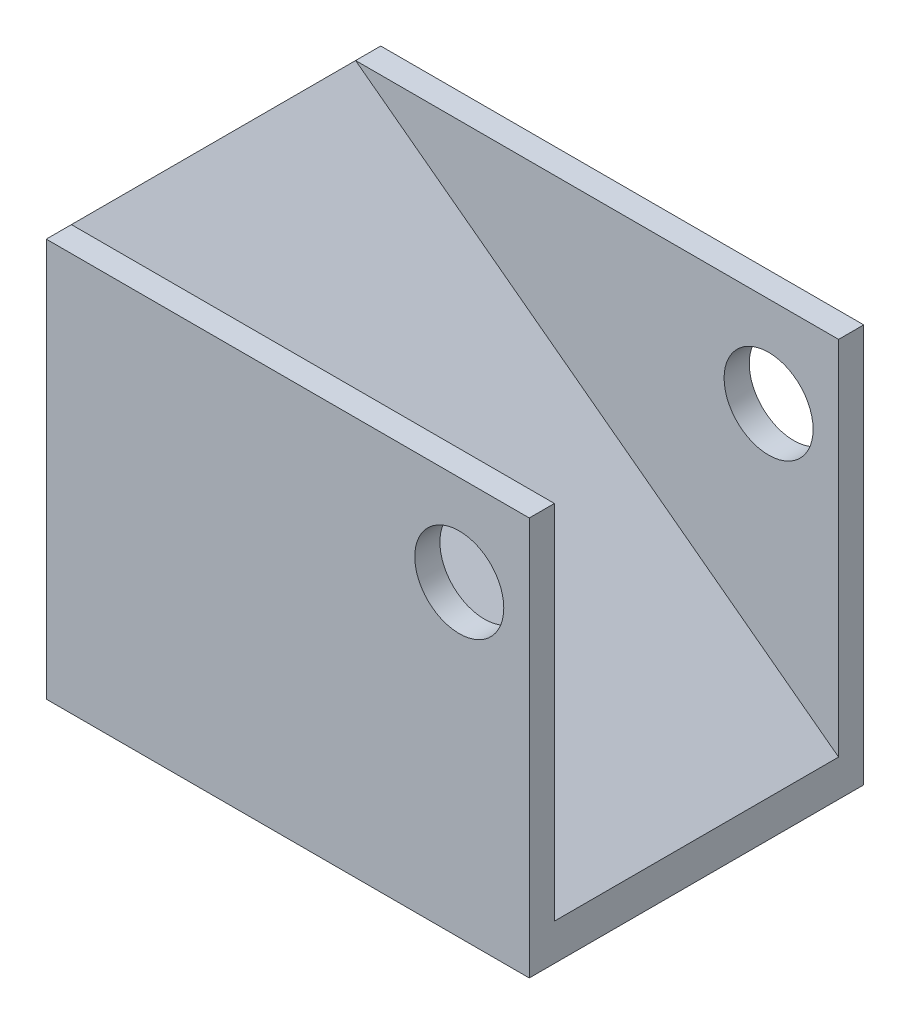
SolidWorks part; units mm, degrees
ref_plane "Front Plane" through (0, 0, 0) normal (0, 0, 1) x (1, 0, 0)
ref_plane "Top Plane" through (0, 0, 0) normal (0, 1, 0) x (1, 0, 0)
ref_plane "Right Plane" through (0, 0, 0) normal (1, 0, 0) x (0, 0, -1)
sketch "Sketch8" plane through (0, 0, 0) normal (0, 1, 0) x (1, 0, 0)
  line L0 (-44.9741, -2.9009) -> (-44.9741, -40.7469)
  line L1 (-44.9741, -40.7469) -> (2.1658, -40.7469)
  line L2 (2.1658, -40.7469) -> (2.1658, -35.808)
  line L3 (2.1658, -2.9009) -> (-44.9741, -2.9009)
  line L4 (2.1658, -7.8398) -> (6.7556, -12.4295)
  line L5 (2.1658, -7.8398) -> (2.1658, -2.9009)
  line L6 (6.7556, -31.2182) -> (2.1658, -35.808)
  line L7 (6.7556, -12.4295) -> (33.8879, -12.4295)
  line L8 (33.8879, -12.4295) -> (33.8879, -31.2182)
  line L9 (33.8879, -31.2182) -> (6.7556, -31.2182)
  line L10 (-44.9741, -21.8239) -> (33.8879, -21.8239) construction
  dimension "D1" = 37.846
  dimension "D2" = 47.1399
  dimension "D3" = 45
  dimension "D4" = 45
  dimension "D5" = 4.5898
  dimension "D6" = 18.923
  dimension "D7" = 4.9389
  dimension "D8" = 78.8619
extrude "Boss-Extrude6" add sketch "Sketch8" along normal blind 2.0599
sketch "Sketch9" plane through (0, 2.0599, 0) normal (0, 1, 0) x (1, 0, 0)
  line L0 (33.8879, -13.8418) -> (6.7556, -13.8418)
  line L1 (33.8879, -31.2182) -> (33.8879, -12.4295) construction
  line L2 (6.7556, -13.8418) -> (6.7556, -12.4295)
  line L3 (6.7556, -12.4295) -> (33.8879, -12.4295)
  line L4 (33.8879, -12.4295) -> (33.8879, -13.8418)
  line L5 (6.7556, -31.2182) -> (6.7556, -29.806)
  line L6 (6.7556, -29.806) -> (33.8879, -29.806)
  line L7 (33.8879, -29.806) -> (33.8879, -31.2182)
  line L8 (33.8879, -31.2182) -> (6.7556, -31.2182)
  dimension "D1" = 1.4122
  dimension "D2" = 1.4122
extrude "Boss-Extrude7" add sketch "Sketch9" along normal blind 20.32
sketch "Sketch10" plane through (0, 0, 31.2182) normal (0, 0, 1) x (1, 0, 0)
  line L0 (6.7556, 0) -> (33.8879, 0) construction
  line L1 (-44.9741, 2.0599) -> (-44.9741, 0) construction
  circle A0 centre (29.9559, 17.2847) radius 2.5006
  dimension "D2" = 74.93
  dimension "D1" = 17.2847
extrude "Cut-Extrude3" cut sketch "Sketch10" against normal blind 25.4
sketch "Sketch14" plane through (0, 0, 13.8418) normal (0, 0, 1) x (1, 0, 0)
  line L0 (6.7556, 22.3799) -> (33.8879, 2.0599)
  line L1 (6.7556, 22.3799) -> (6.7556, 19.8268)
  line L2 (6.7556, 22.3799) -> (6.7556, 2.0599) construction
  line L3 (6.7556, 19.8268) -> (30.5689, 2.0599)
  line L4 (30.5689, 2.0599) -> (33.8879, 2.0599)
extrude "Boss-Extrude10" add sketch "Sketch14" along normal blind 16.0299
sketch "Sketch15" plane through (0, 2.0599, 0) normal (0, 1, 0) x (1, 0, 0)
  line L0 (6.7556, -29.806) -> (6.7556, -13.8418) construction
  line L1 (-44.9741, -40.7469) -> (6.7556, -40.7469)
  line L2 (-44.9741, -40.7469) -> (-44.9741, -2.9009)
  line L3 (-44.9741, -2.9009) -> (6.7556, -2.9009)
  line L4 (6.7556, -40.7469) -> (6.7556, -2.9009)
  line L5 (2.1658, -2.9009) -> (-44.9741, -2.9009) construction
extrude "Cut-Extrude5" cut sketch "Sketch15" against normal through all
